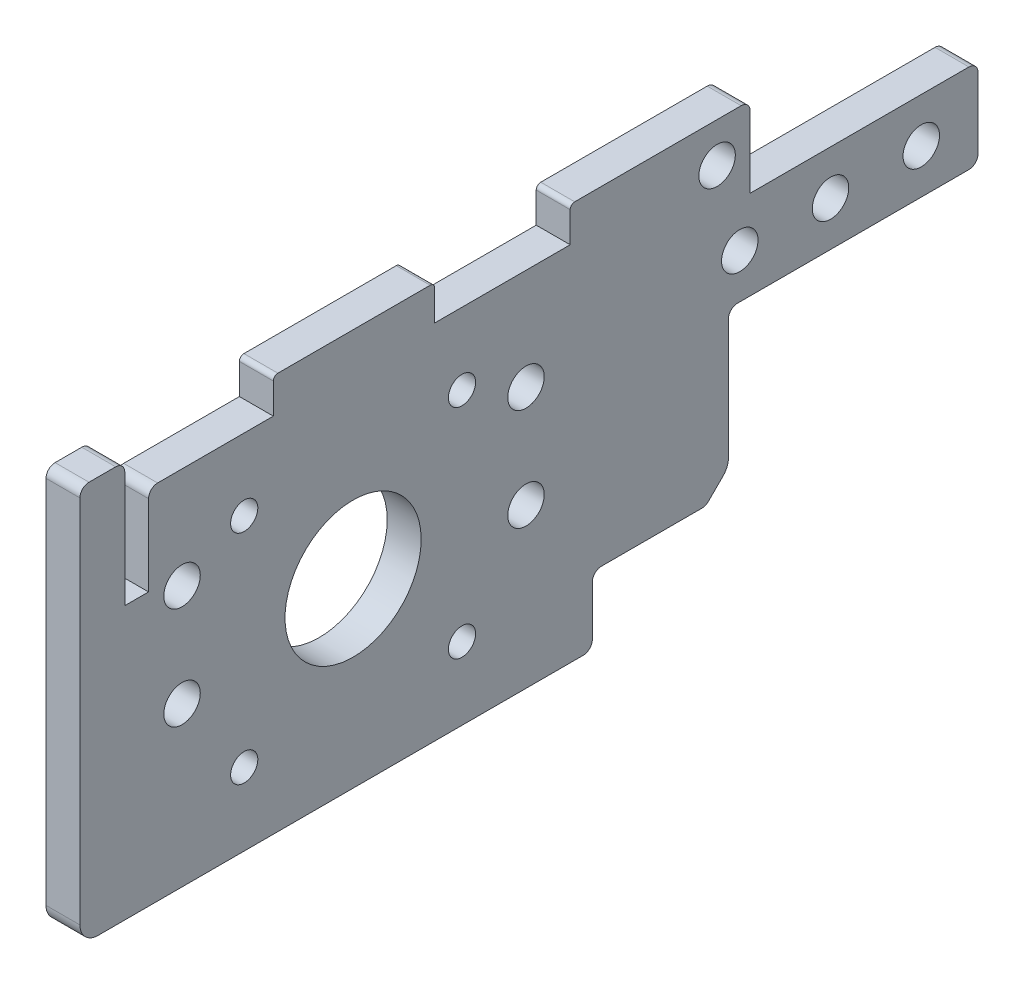
SolidWorks part; units mm, degrees
material "AISI Type A2 Tool Steel"
ref_plane "Front Plane" through (0, 0, 0) normal (0, 0, 1) x (1, 0, 0)
ref_plane "Top Plane" through (0, 0, 0) normal (0, 1, 0) x (1, 0, 0)
ref_plane "Right Plane" through (0, 0, 0) normal (1, 0, 0) x (0, 0, -1)
sketch "Top Layout" plane through (0, 0, 0) normal (0, 1, 0) x (1, 0, 0)
  line L0 (-114.046, -123.825) -> (-104.775, -123.825) construction
  line L1 (-104.775, -142.875) -> (-101.6, -142.875)
  line L2 (-104.775, -142.875) -> (-104.775, -104.775)
  line L3 (-104.775, -104.775) -> (-101.6, -104.775)
  line L4 (-101.6, -142.875) -> (-101.6, -104.775)
  line L5 (-104.775, -142.875) -> (-101.6, -104.775) construction
  line L6 (-104.775, -104.775) -> (-101.6, -142.875) construction
  line L7 (-19.05, -105.8164) -> (-101.6, -105.8164)
  line L8 (-19.05, -105.8164) -> (-19.05, -141.8336)
  line L9 (-19.05, -141.8336) -> (-101.6, -141.8336)
  line L10 (-101.6, -105.8164) -> (-101.6, -141.8336)
  line L11 (-19.05, -105.8164) -> (-101.6, -141.8336) construction
  line L12 (-19.05, -141.8336) -> (-101.6, -105.8164) construction
  line L13 (-133.096, -85.725) -> (-114.046, -85.725)
  line L14 (-133.096, -85.725) -> (-133.096, -161.925)
  line L15 (-133.096, -161.925) -> (-114.046, -161.925)
  line L16 (-114.046, -85.725) -> (-114.046, -161.925)
  line L17 (-133.096, -85.725) -> (-114.046, -161.925) construction
  line L18 (-133.096, -161.925) -> (-114.046, -85.725) construction
  line L19 (-104.775, -123.825) -> (0, -123.825) construction
  line L20 (0, -123.825) -> (0, 0) construction
  line L21 (-52.3528, -40.1717) -> (0, 0) construction
  line L22 (-70.6449, -16.3328) -> (-18.2922, 23.8388)
  line L23 (-34.0606, -64.0105) -> (18.2922, -23.8388)
  line L24 (-30.9251, 40.3023) -> (-122.2248, -29.7544)
  line L25 (-153.9748, -53.975) -> (-153.9748, -123.825)
  line L26 (-109.5248, -162.052) -> (109.5248, -162.052)
  line L27 (0, -162.052) -> (0, -123.825) construction
  line L28 (-109.5248, -162.052) -> (-109.5248, -20.0093) construction
  line L29 (-104.775, -142.875) -> (-104.775, -152.527)
  line L30 (-104.775, -152.527) -> (104.775, -152.527)
  line L31 (104.775, -104.775) -> (101.6, -104.775)
  line L32 (-144.4498, -73.025) -> (-109.5248, -73.025)
  line L33 (-144.4498, -73.025) -> (-144.4498, -123.825)
  line L34 (-144.4498, -123.825) -> (-109.5248, -123.825) construction
  line L35 (-109.5248, -73.025) -> (-109.5248, -162.052)
  line L36 (-144.4498, -73.025) -> (-109.5248, -123.825) construction
  line L37 (-144.4498, -123.825) -> (-109.5248, -73.025) construction
  line L38 (101.6, -142.875) -> (101.6, -104.775)
  line L39 (104.775, -142.875) -> (101.6, -142.875)
  line L40 (104.775, -142.875) -> (104.775, -104.775)
  line L41 (104.775, -142.875) -> (104.775, -152.527)
  line L42 (109.5248, -162.052) -> (109.5248, -20.0093) construction
  line L43 (30.9251, 40.3023) -> (122.2248, -29.7544)
  line L45 (19.05, -141.8336) -> (101.6, -141.8336)
  line L46 (101.6, -105.8164) -> (101.6, -141.8336)
  line L47 (19.05, -105.8164) -> (101.6, -105.8164)
  line L48 (19.05, -105.8164) -> (19.05, -141.8336)
  line L49 (133.096, -161.925) -> (114.046, -161.925)
  line L50 (114.046, -85.725) -> (114.046, -161.925)
  line L51 (133.096, -85.725) -> (114.046, -85.725)
  line L52 (133.096, -85.725) -> (133.096, -161.925)
  line L53 (144.4498, -123.825) -> (109.5248, -123.825) construction
  line L54 (109.5248, -73.025) -> (109.5248, -162.052)
  line L55 (144.4498, -73.025) -> (109.5248, -73.025)
  line L56 (144.4498, -73.025) -> (144.4498, -123.825)
  line L57 (-109.5248, -123.825) -> (-109.5248, -162.052) construction
  line L62 (-153.9748, -53.975) -> (-122.2248, -53.975)
  line L63 (-122.2248, -53.975) -> (-122.2248, -29.7544)
  line L64 (-144.4498, -123.825) -> (-153.9748, -123.825)
  line L65 (153.9748, -53.975) -> (153.9748, -123.825)
  line L66 (109.5248, -123.825) -> (109.5248, -162.052) construction
  line L67 (144.4498, -123.825) -> (153.9748, -123.825)
  line L68 (122.2248, -29.7544) -> (122.2248, -53.975)
  line L73 (-104.775, -104.775) -> (-104.775, -16.3647) construction
  line L74 (-95.25, -162.052) -> (-95.25, -9.0559) construction
  line L75 (-109.5248, -162.052) -> (-109.5248, -123.825) construction
  line L76 (109.5248, -162.052) -> (109.5248, -123.825) construction
  line L77 (122.2248, -53.975) -> (153.9748, -53.975)
  line L83 (104.775, -155.5496) -> (-104.775, -155.5496) construction
  line L88 (95.25, -162.052) -> (95.25, -9.0559) construction
  line L89 (104.775, -104.775) -> (104.775, -16.3647) construction
  line L92 (-104.775, -152.527) -> (-104.775, -162.052) construction
  line L93 (-14.605, -76.327) -> (14.605, -76.327)
  line L94 (-14.605, -76.327) -> (-14.605, -152.527)
  line L95 (-14.605, -152.527) -> (14.605, -152.527)
  line L96 (14.605, -76.327) -> (14.605, -152.527)
  line L97 (-14.605, -76.327) -> (14.605, -152.527) construction
  line L98 (-14.605, -152.527) -> (14.605, -76.327) construction
  line L99 (104.775, -152.527) -> (104.775, -162.052) construction
  line L100 (-19.05, -105.8164) -> (0, -105.8164) construction
  line L107 (0, -105.8164) -> (19.05, -105.8164) construction
  line L108 (104.775, -123.825) -> (114.046, -123.825) construction
  circle A0 centre (0, 0) radius 114.3
  circle A1 centre (0, 0) radius 6.35
  circle A2 centre (-52.3528, -40.1717) radius 17.8
  circle A3 centre (0, 0) radius 30.0482
  circle A4 centre (-52.3528, -40.1717) radius 30.0482
  arc A5 (-30.9251, 40.3023) -> (30.9251, 40.3023) centre (0, 0) cw
  point P2 (-103.1875, -123.825)
  point P7 (-60.325, -123.825)
  point P12 (-123.571, -123.825)
  point P30 (-126.9873, -98.425)
  point P35 (0, -114.427)
  point P53 (0, -152.527)
  dimension "D1" = 35.6
  dimension "D2" = 12.7
  dimension "D3" = 228.6
  dimension "D11" = 60.0964
  dimension "D12" = 50.8
  dimension "D14" = 52.5
  dimension "D4" = 3.175
  dimension "D5" = 19.05
  dimension "D6" = 76.2
  dimension "D7" = 82.55
  dimension "D8" = 38.1
  dimension "D9" = 104.775
  dimension "D10" = 18.0086
  dimension "D13" = 9.525
  dimension "D15" = 4.7498
  dimension "D16" = 9.525
  dimension "D17" = 9.652
  dimension "D18" = 50.8
  dimension "D19" = 12.446
  dimension "D20" = 65.9892
  dimension "D21" = 19.05
  dimension "D22" = 34.925
  dimension "D23" = 123.825
  dimension "D24" = 12.7
  dimension "D25" = 9.525
  dimension "D26" = 29.21
  dimension "D27" = 76.2
  dimension "D28" = 3.0226
sketch "Side Layout" plane through (0, 0, 0) normal (1, 0, 0) x (0, 0, -1)
  line L0 (0, -38.1) -> (0, 33.7344) construction
  line L1 (-114.3, -20.955) -> (114.3, -20.955)
  line L2 (-114.3, -20.955) -> (-114.3, -33.655)
  line L3 (-114.3, -33.655) -> (114.3, -33.655)
  line L4 (114.3, -20.955) -> (114.3, -33.655)
  line L5 (-114.3, -20.955) -> (114.3, -33.655) construction
  line L6 (-114.3, -33.655) -> (114.3, -20.955) construction
  line L7 (-9.525, -32.9406) -> (9.525, -32.9406)
  line L8 (-9.525, -32.9406) -> (-9.525, -38.1)
  line L9 (-9.525, -38.1) -> (9.525, -38.1)
  line L10 (9.525, -32.9406) -> (9.525, -38.1)
  line L11 (-9.525, -32.9406) -> (9.525, -38.1) construction
  line L12 (-9.525, -38.1) -> (9.525, -32.9406) construction
  line L13 (-11.9126, -29.3338) -> (11.9126, -29.3338)
  line L14 (-11.9126, -29.3338) -> (-11.9126, -32.9406)
  line L15 (-11.9126, -32.9406) -> (11.9126, -32.9406)
  line L16 (11.9126, -29.3338) -> (11.9126, -32.9406)
  line L17 (-11.9126, -29.3338) -> (11.9126, -32.9406) construction
  line L18 (-11.9126, -32.9406) -> (11.9126, -29.3338) construction
  line L19 (-6.35, -32.9406) -> (6.35, -32.9406)
  line L20 (-6.35, -32.9406) -> (-6.35, 33.7344)
  line L21 (-6.35, 33.7344) -> (6.35, 33.7344)
  line L22 (6.35, -32.9406) -> (6.35, 33.7344)
  line L23 (-6.35, -32.9406) -> (6.35, 33.7344) construction
  line L24 (-6.35, 33.7344) -> (6.35, -32.9406) construction
  line L25 (-162.052, 0) -> (-123.825, 0) construction
  line L26 (114.3, -33.655) -> (114.3, 0) construction
  line L27 (-142.875, 19.05) -> (-104.775, 19.05)
  line L28 (-40.1717, -9.525) -> (-40.1717, 5.4) construction
  line L29 (-142.875, 19.05) -> (-142.875, -19.05)
  line L30 (-142.875, -19.05) -> (-104.775, -19.05)
  line L31 (-104.775, 19.05) -> (-104.775, -19.05)
  line L32 (-142.875, 19.05) -> (-104.775, -19.05) construction
  line L33 (-142.875, -19.05) -> (-104.775, 19.05) construction
  line L34 (-130.175, -38.1) -> (-117.9516, -38.1) construction
  line L35 (-57.9717, -14.6) -> (-22.3717, -14.6)
  line L36 (-30.0482, -2.794) -> (30.0482, -2.794)
  line L37 (-30.0482, -2.794) -> (-30.0482, -20.955)
  line L38 (-30.0482, -20.955) -> (30.0482, -20.955)
  line L39 (30.0482, -2.794) -> (30.0482, -20.955)
  line L40 (-30.0482, -2.794) -> (30.0482, -20.955) construction
  line L41 (-30.0482, -20.955) -> (30.0482, -2.794) construction
  line L42 (-30.0482, -2.794) -> (-30.0482, 0) construction
  line L43 (-123.825, 0) -> (0, 0) construction
  line L44 (-57.9717, -14.6) -> (-57.9717, 25.4)
  line L45 (-57.9717, 25.4) -> (-22.3717, 25.4)
  line L46 (-22.3717, -14.6) -> (-22.3717, 25.4)
  line L47 (-19.05, 0) -> (19.05, 0)
  line L48 (-19.05, 0) -> (-19.05, -1.9812)
  line L49 (-19.05, -1.9812) -> (19.05, -1.9812)
  line L50 (19.05, 0) -> (19.05, -1.9812)
  line L51 (-19.05, 0) -> (19.05, -1.9812) construction
  line L52 (-19.05, -1.9812) -> (19.05, 0) construction
  line L53 (-70.2199, -3.175) -> (-10.1235, -3.175)
  line L54 (-70.2199, -3.175) -> (-70.2199, -15.875)
  line L55 (-70.2199, -15.875) -> (-10.1235, -15.875)
  line L56 (-10.1235, -3.175) -> (-10.1235, -15.875)
  line L57 (-70.2199, -3.175) -> (-10.1235, -15.875) construction
  line L58 (-70.2199, -15.875) -> (-10.1235, -3.175) construction
  line L59 (-40.1717, -9.525) -> (-40.1717, 0) construction
  line L60 (-57.9717, -14.6) -> (-22.3717, 25.4) construction
  line L61 (-57.9717, 25.4) -> (-22.3717, -14.6) construction
  line L62 (-22.3717, 0) -> (-57.9717, 0) construction
  line L63 (-137.8162, 0) -> (-123.825, -13.9912) construction
  line L64 (-139.065, 15.24) -> (-108.585, 15.24) construction
  line L65 (-139.065, 15.24) -> (-139.065, -15.24) construction
  line L66 (-139.065, -15.24) -> (-108.585, -15.24) construction
  line L67 (-108.585, 15.24) -> (-108.585, -15.24) construction
  line L68 (-139.065, 15.24) -> (-108.585, -15.24) construction
  line L69 (-139.065, -15.24) -> (-108.585, 15.24) construction
  line L70 (-137.8162, 0) -> (-123.825, 13.9912) construction
  line L71 (-123.825, -13.9912) -> (-109.8338, 0) construction
  line L72 (-123.825, 13.9912) -> (-109.8338, 0) construction
  line L73 (-137.8162, 0) -> (-109.8338, 0) construction
  line L74 (-123.825, -13.9912) -> (-123.825, 13.9912) construction
  line L75 (-6.35, 17.8594) -> (6.35, 17.8594)
  line L76 (114.3, 0) -> (-114.3, 0) construction
  line L77 (-22.3717, 19.05) -> (-6.35, 19.05) construction
  line L78 (-123.825, 38.1) -> (-97.9206, 38.1) construction
  line L79 (-19.05, -3.5814) -> (19.05, -3.5814)
  line L80 (-19.05, -3.5814) -> (-19.05, -1.9812)
  line L81 (-19.05, -1.9812) -> (19.05, -1.9812)
  line L82 (19.05, -3.5814) -> (19.05, -1.9812)
  line L83 (-19.05, -3.5814) -> (19.05, -1.9812) construction
  line L84 (-19.05, -1.9812) -> (19.05, -3.5814) construction
  line L85 (-8.7376, -16.7608) -> (8.7376, -16.7608)
  line L86 (-8.7376, -16.7608) -> (-8.7376, -29.3338)
  line L87 (-8.7376, -29.3338) -> (8.7376, -29.3338)
  line L88 (8.7376, -16.7608) -> (8.7376, -29.3338)
  line L89 (-8.7376, -16.7608) -> (8.7376, -29.3338) construction
  line L90 (-8.7376, -29.3338) -> (8.7376, -16.7608) construction
  line L91 (-8.7376, -3.5814) -> (8.7376, -3.5814)
  line L92 (-8.7376, -3.5814) -> (-8.7376, -16.1544)
  line L93 (-8.7376, -16.1544) -> (8.7376, -16.1544)
  line L94 (8.7376, -3.5814) -> (8.7376, -16.1544)
  line L95 (-8.7376, -3.5814) -> (8.7376, -16.1544) construction
  line L96 (-8.7376, -16.1544) -> (8.7376, -3.5814) construction
  circle A0 centre (-123.825, 0) radius 18.0086
  circle A1 centre (-123.825, 0) radius 38.1
  circle A2 centre (-139.065, 15.24) radius 1.905
  circle A3 centre (-108.585, 15.24) radius 1.905
  circle A4 centre (-108.585, -15.24) radius 1.905
  circle A5 centre (-139.065, -15.24) radius 1.905
  circle A6 centre (-137.8162, 0) radius 1.6002
  circle A7 centre (-123.825, 13.9912) radius 1.6002
  circle A8 centre (-109.8338, 0) radius 1.6002
  circle A9 centre (-123.825, -13.9912) radius 1.6002
  point P0 (0, -27.305)
  point P6 (0, -31.1372)
  point P7 (0, -35.5203)
  point P21 (0, 0.3969)
  point P32 (0, -11.8745)
  point P43 (0, -0.9906)
  point P55 (-40.1717, -9.525)
  point P72 (-40.1717, 5.4)
  point P88 (0, -23.0473)
  point P93 (0, -2.7813)
  point P102 (0, -9.8679)
  dimension "D17" = 3.81
  dimension "D18" = 3.2004
  dimension "D1" = 12.7
  dimension "D2" = 5.1594
  dimension "D3" = 19.05
  dimension "D4" = 3.6068
  dimension "D5" = 23.8252
  dimension "D6" = 12.7
  dimension "D7" = 18.161
  dimension "D8" = 1.9812
  dimension "D9" = 12.7
  dimension "D10" = 40
  dimension "D11" = 25.4
  dimension "D12" = 50.8
  dimension "D13" = 41.275
  dimension "D14" = 30.48
  dimension "D15" = 4.445
  dimension "D16" = 19.7866
  dimension "D19" = 15.875
  dimension "D20" = 6.35
  dimension "D21" = 38.1
  dimension "D22" = 1.6002
  dimension "D23" = 38.1
  dimension "D24" = 17.4752
  dimension "D25" = 12.573
ref_plane "Plane1" through (0, 25.4, 0) normal (0, 1, 0) x (1, 0, 0)
sketch "Sketch3" plane through (0, 25.4, 0) normal (0, 1, 0) x (1, 0, 0)
  line L0 (-104.775, -36.3747) -> (-30.9251, 20.2924)
  line L1 (-104.775, -104.775) -> (-104.775, -16.3647) construction
  line L2 (0, -200130.175) -> (0, 199882.0484) construction
  line L3 (-30.9251, 40.3023) -> (-122.2248, -29.7544) construction
  line L5 (-104.775, -36.3747) -> (-104.775, -77.6497)
  line L6 (-92.075, -77.6497) -> (-104.775, -77.6497)
  line L7 (30.9251, 20.2924) -> (104.775, -36.3747)
  line L8 (104.775, -77.6497) -> (92.075, -77.6497)
  line L9 (104.775, -36.3747) -> (104.775, -77.6497)
  line L11 (104.775, -104.775) -> (104.775, -16.3647) construction
  line L12 (30.9251, 40.3023) -> (122.2248, -29.7544) construction
  line L13 (92.075, -74.6536) -> (24.1423, -22.5271)
  line L14 (-32.2514, -66.3682) -> (20.1013, -26.1965)
  line L15 (-30.9251, 20.2924) -> (0, 44.022)
  line L16 (0, 44.022) -> (30.9251, 20.2924)
  line L17 (-92.075, -77.6497) -> (-92.075, -73.1917)
  line L19 (-92.075, -73.1917) -> (-52.3528, -73.1917)
  line L20 (92.075, -74.6536) -> (92.075, -77.6497)
  circle A0 centre (-52.3528, -40.1717) radius 17.8 construction
  circle A1 centre (-52.3528, -40.1717) radius 17.8
  circle A2 centre (0, 0) radius 6.35
  circle A3 centre (0, 0) radius 6.35 construction
  arc A4 (-52.3528, -73.1917) -> (-32.2514, -66.3682) centre (-52.3528, -40.1717) ccw
  arc A5 (20.1013, -26.1965) -> (24.1423, -22.5271) centre (0, 0) ccw
  arc A6 (30.9251, 20.2924) -> (-30.9251, 20.2924) centre (0, -20.01) ccw construction
  point P28 (0, 44.022)
  dimension "D1" = 33.02
  dimension "D5" = 50.8
  dimension "D2" = 41.275
  dimension "D3" = 34.925
  dimension "D4" = 12.7
  dimension "D6" = 38.1
ref_plane "Plane3" through (-104.775, 0, 0) normal (-1, 0, 0) x (0, 0, 1)
sketch "Sketch6" plane through (-104.775, 0, 0) normal (-1, 0, 0) x (0, 0, 1)
  line L0 (162.052, -25.4) -> (162.052, 25.4)
  line L1 (162.052, 25.4) -> (77.6497, 25.4)
  line L2 (36.3747, 25.4) -> (77.6497, 25.4) construction
  line L3 (147.7645, 11.1125) -> (162.052, 11.1125) construction
  line L4 (162.052, 0) -> (71.2997, 0) construction
  line L5 (77.6497, 25.4) -> (77.6497, 19.05)
  line L6 (77.6497, 19.05) -> (36.3747, 19.05)
  line L7 (36.3747, 19.05) -> (36.3747, 6.35)
  line L8 (36.3747, 6.35) -> (71.2997, 6.35)
  line L10 (99.6315, -3.175) -> (99.6315, 11.1125) construction
  line L11 (71.2997, -25.4) -> (162.052, -25.4)
  line L13 (71.2997, 6.35) -> (71.2997, -25.4)
  line L14 (152.527, -25.4) -> (152.527, 25.4) construction
  line L15 (99.6315, 11.1125) -> (99.6315, 25.4) construction
  line L16 (147.7645, 11.1125) -> (147.7645, 25.4) construction
  line L17 (94.869, -7.9375) -> (104.394, -7.9375) construction
  line L18 (94.869, -7.9375) -> (94.869, 25.4) construction
  line L19 (94.869, 25.4) -> (104.394, 25.4) construction
  line L20 (104.394, -7.9375) -> (104.394, 25.4) construction
  line L21 (94.869, -7.9375) -> (104.394, 25.4) construction
  line L22 (94.869, 25.4) -> (104.394, -7.9375) construction
  line L23 (147.7645, 11.1125) -> (147.7645, -3.175) construction
  line L24 (104.394, -7.9375) -> (123.825, -7.9375) construction
  line L25 (143.002, -7.9375) -> (152.527, -7.9375) construction
  line L26 (143.002, -7.9375) -> (143.002, 25.4) construction
  line L27 (143.002, 25.4) -> (152.527, 25.4) construction
  line L28 (152.527, -7.9375) -> (152.527, 25.4) construction
  line L29 (143.002, -7.9375) -> (152.527, 25.4) construction
  line L30 (143.002, 25.4) -> (152.527, -7.9375) construction
  line L31 (123.825, -7.9375) -> (152.527, -7.9375) construction
  line L32 (104.775, 19.05) -> (104.775, -19.05) construction
  line L34 (155.702, -25.4) -> (155.702, 25.4) construction
  circle A0 centre (109.8338, 0) radius 1.6002 construction
  circle A1 centre (123.825, 13.9912) radius 1.6002 construction
  circle A2 centre (137.8162, 0) radius 1.6002 construction
  circle A3 centre (123.825, -13.9912) radius 1.6002 construction
  circle A4 centre (109.8338, 0) radius 1.6002 construction
  circle A5 centre (123.825, 13.9912) radius 1.6002 construction
  circle A6 centre (137.8162, 0) radius 1.6002 construction
  circle A7 centre (123.825, -13.9912) radius 1.6002 construction
  circle A8 centre (123.825, 0) radius 18.0086 construction
  circle A9 centre (123.825, 0) radius 18.0086 construction
  circle A10 centre (123.825, 0) radius 9.525
  circle A11 centre (108.585, -15.24) radius 1.905 construction
  circle A12 centre (108.585, 15.24) radius 1.905 construction
  circle A13 centre (139.065, 15.24) radius 1.905 construction
  circle A14 centre (139.065, -15.24) radius 1.905 construction
  circle A15 centre (108.585, -15.24) radius 1.905
  circle A16 centre (108.585, 15.24) radius 1.905
  circle A17 centre (139.065, 15.24) radius 1.905
  circle A18 centre (139.065, -15.24) radius 1.905
  circle A19 centre (147.7645, 11.1125) radius 2.5527
  circle A26 centre (99.6315, 11.1125) radius 2.5527
  circle A27 centre (99.6315, -3.175) radius 2.5527
  circle A28 centre (147.7645, -3.175) radius 2.5527
  point P29 (0, 0)
  point P55 (99.6315, 8.7312)
  point P61 (147.7645, 8.7312)
  dimension "D4" = 19.05
  dimension "D7" = 5.1054
  dimension "D1" = 6.35
  dimension "D2" = 12.7
  dimension "D3" = 25.4
  dimension "D5" = 6.35
  dimension "D6" = 3.175
  dimension "D8" = 0.381
  dimension "D9" = 14.2875
  dimension "D10" = 9.525
  dimension "D12" = 33.3375
extrude "Side Plate Extrude" add sketch "Sketch6" along normal up to vertex (4.7498 mm away) up to point (-109.5248, 0, 73.025)
sketch "Sketch12" [suppressed] plane through (0, 19.05, 0) normal (0, 1, 0) x (1, 0, 0)
  line L0 (-104.775, -77.6497) -> (-104.775, -36.3747)
  line L1 (-104.775, -36.3747) -> (-92.075, -36.3747)
  line L3 (-92.075, -36.3747) -> (-92.075, -77.6497)
  line L5 (-92.075, -77.6497) -> (-104.775, -77.6497)
  line L6 (-98.425, -77.6497) -> (-98.425, -63.3622) construction
  line L7 (-98.425, -63.3622) -> (-98.425, -50.6622) construction
  line L8 (-98.425, -50.6622) -> (-98.425, -36.3747) construction
  line L10 (-98.425, -36.3747) -> (-104.775, -36.3747) construction
  circle A0 centre (-98.425, -63.3622) radius 2.5527
  circle A1 centre (-98.425, -50.6622) radius 2.5527
  dimension "D2" = 5.1054
  dimension "D1" = 12.7
  dimension "D3" = 12.7
sketch "Sketch15" plane through (-109.5248, 0, 0) normal (-1, 0, 0) x (0, 0, 1)
  line L0 (36.3747, 12.7) -> (44.3122, 12.7) construction
  line L1 (36.3747, 19.05) -> (36.3747, 6.35) construction
  line L2 (44.3122, 12.7) -> (57.0122, 12.7) construction
  line L3 (57.0122, 12.7) -> (69.7122, 12.7) construction
  line L4 (69.7122, 12.7) -> (77.6497, 12.7) construction
  line L5 (77.6497, 12.7) -> (77.6497, 19.05) construction
  circle A0 centre (44.3122, 12.7) radius 2.5527
  circle A1 centre (57.0122, 12.7) radius 2.5527
  circle A2 centre (69.7122, 12.7) radius 2.5527
  dimension "D1" = 5.1054
  dimension "D2" = 12.7
extrude "Custom Nutstrip Holes" cut sketch "Sketch15" against normal through all
ref_plane "Plane5" through (0, 0, 152.527) normal (0, 0, 1) x (1, 0, 0)
sketch "Sketch41" plane through (0, 0, 152.527) normal (0, 0, 1) x (1, 0, 0)
  line L0 (-104.775, -7.9375) -> (-104.775, 25.4) construction
  line L1 (-104.775, -7.9375) -> (-104.775, 12.7)
  line L2 (-104.775, -7.9375) -> (104.775, -7.9375)
  line L3 (104.775, -7.9375) -> (104.775, 12.7)
  line L4 (104.775, 25.4) -> (-104.775, 25.4)
  line L5 (0, -7.9375) -> (0, 25.4) construction
  line L6 (-104.775, 3.9624) -> (-100.0125, 3.9624) construction
  line L7 (-100.0125, 3.9624) -> (-100.0125, 25.4) construction
  line L8 (104.775, 3.9624) -> (100.0125, 3.9624) construction
  line L9 (100.0125, 3.9624) -> (100.0125, 25.4) construction
  line L10 (19.05, 20.6375) -> (23.8252, 20.6375) construction
  line L11 (19.05, 15.875) -> (78.5876, 15.875) construction
  line L12 (19.05, 15.875) -> (19.05, 25.4) construction
  line L13 (19.05, 25.4) -> (78.5876, 25.4) construction
  line L14 (78.5876, 15.875) -> (78.5876, 25.4) construction
  line L15 (19.05, 15.875) -> (78.5876, 25.4) construction
  line L16 (19.05, 25.4) -> (78.5876, 15.875) construction
  line L17 (23.8252, 20.6375) -> (38.1127, 20.6375) construction
  line L18 (38.1127, 20.6375) -> (52.4002, 20.6375) construction
  line L19 (52.4002, 20.6375) -> (66.6877, 20.6375) construction
  line L20 (-104.775, 25.4) -> (-112.395, 25.4)
  line L21 (-112.395, 25.4) -> (-112.395, 3.175)
  line L22 (-112.395, 3.175) -> (-109.5248, 3.175)
  line L23 (-109.5248, 3.175) -> (-109.5248, 12.7)
  line L24 (-109.5248, 12.7) -> (-104.775, 12.7)
  line L25 (-104.775, 12.7) -> (-104.775, 25.4) construction
  line L26 (104.775, 25.4) -> (112.395, 25.4)
  line L27 (112.395, 25.4) -> (112.395, 3.175)
  line L28 (112.395, 3.175) -> (109.5248, 3.175)
  line L29 (109.5248, 3.175) -> (109.5248, 12.7)
  line L30 (109.5248, 12.7) -> (104.775, 12.7)
  line L31 (104.775, 12.7) -> (104.775, 25.4) construction
  line L32 (-100.0125, 3.9624) -> (-87.3125, 3.9624) construction
  line L33 (-63.5, -1.5875) -> (0, -1.5875) construction
  line L34 (0, -1.5875) -> (63.5, -1.5875) construction
  line L35 (63.5, -1.5875) -> (63.5, -7.9375) construction
  circle A0 centre (-100.0125, 3.9624) radius 2.5527
  circle A1 centre (100.0125, 3.9624) radius 2.5527
  circle A2 centre (23.8252, 20.6375) radius 2.5527
  circle A3 centre (38.1127, 20.6375) radius 2.5527
  circle A4 centre (52.4002, 20.6375) radius 2.5527
  circle A5 centre (66.6877, 20.6375) radius 2.5527
  circle A6 centre (-66.6877, 20.6375) radius 2.5527
  circle A7 centre (-52.4002, 20.6375) radius 2.5527
  circle A8 centre (-38.1127, 20.6375) radius 2.5527
  circle A9 centre (-23.8252, 20.6375) radius 2.5527
  circle A10 centre (-87.3125, 3.9624) radius 2.5527
  circle A11 centre (87.3125, 3.9624) radius 2.5527
  circle A12 centre (-63.5, -1.5875) radius 2.5527
  circle A13 centre (63.5, -1.5875) radius 2.5527
  point P14 (48.8188, 20.6375)
  dimension "D3" = 5.1054
  dimension "D7" = 5.1054
  dimension "D1" = 21.4376
  dimension "D2" = 4.7625
  dimension "D4" = 9.525
  dimension "D5" = 59.5376
  dimension "D6" = 4.7752
  dimension "D8" = 14.2875
  dimension "D9" = 7.62
  dimension "D10" = 4.7498
  dimension "D11" = 12.7
  dimension "D12" = 9.525
  dimension "D13" = 19.05
  dimension "D14" = 12.7
  dimension "D15" = 6.35
  dimension "D16" = 63.5
sketch "Sketch43" plane through (-109.5248, 0, 0) normal (-1, 0, 0) x (0, 0, 1)
  line L1 (152.527, 12.7) -> (155.702, 12.7)
  line L2 (152.527, 12.7) -> (152.527, 25.4)
  line L3 (152.527, 25.4) -> (155.702, 25.4)
  line L4 (155.702, 12.7) -> (155.702, 25.4)
  line L5 (152.527, 12.7) -> (155.702, 25.4) construction
  line L6 (152.527, 25.4) -> (155.702, 12.7) construction
  line L7 (162.052, 25.4) -> (77.6497, 25.4) construction
  point P4 (154.1145, 19.05)
  dimension "D1" = 3.175
extrude "Cut-Extrude19" cut sketch "Sketch43" against normal through all
sketch "Sketch44" plane through (0, 25.4, 0) normal (0, 1, 0) x (1, 0, 0)
  line L0 (73.8315, -147.7645) -> (73.8315, -152.527) construction
  line L1 (92.075, -74.6536) -> (92.075, -77.6497) construction
  line L2 (-92.075, -77.6497) -> (-92.075, -73.1917) construction
  line L3 (0, -123.825) -> (0, 0) construction
  line L4 (-92.075, -73.1917) -> (-52.3528, -73.1917) construction
  line L5 (-104.775, -104.775) -> (-104.775, -16.3647) construction
  line L6 (-32.2514, -66.3682) -> (20.1013, -26.1965) construction
  line L21 (-104.775, -68.1247) -> (-104.775, -152.527)
  line L22 (-104.775, -152.527) -> (104.775, -152.527)
  line L23 (104.775, -152.527) -> (104.775, -68.1247)
  line L34 (-104.775, -99.6315) -> (-100.0125, -99.6315) construction
  line L35 (-104.775, -147.7645) -> (-100.0125, -147.7645) construction
  line L36 (0, -152.527) -> (0, -35.6178) construction
  line L38 (30.969, -147.7645) -> (45.2565, -147.7645) construction
  line L39 (45.2565, -147.7645) -> (59.544, -147.7645) construction
  line L40 (59.544, -147.7645) -> (73.8315, -147.7645) construction
  line L41 (23.8252, -152.527) -> (30.969, -152.527) construction
  line L42 (104.775, -152.527) -> (-104.775, -152.527) construction
  line L43 (30.969, -152.527) -> (38.1127, -152.527) construction
  line L44 (30.969, -152.527) -> (30.969, -147.7645) construction
  line L45 (-92.075, -77.6497) -> (-104.775, -77.6497) construction
  line L48 (-35.1507, -62.5899) -> (-8.9743, -42.504) construction
  line L49 (-8.9743, -42.504) -> (17.2021, -22.4182) construction
  line L50 (45.5313, -32.9364) -> (87.3125, -64.9962) construction
  line L51 (92.075, -74.6536) -> (24.1423, -22.5271) construction
  line L52 (104.775, -77.6497) -> (92.075, -77.6497) construction
  line L79 (-104.775, -68.1247) -> (-92.075, -68.1247)
  line L80 (-92.075, -68.1247) -> (-92.075, -63.6667)
  line L85 (21.8118, -8.7328) -> (92.075, -62.6476)
  line L86 (-38.0499, -58.8115) -> (14.3028, -18.6398)
  line L87 (-92.075, -63.6667) -> (-52.3528, -63.6667)
  line L88 (92.075, -62.6476) -> (92.075, -68.1247)
  line L89 (92.075, -68.1247) -> (104.775, -68.1247)
  circle A0 centre (-73.8315, -147.7645) radius 2.5527
  circle A1 centre (-59.544, -147.7645) radius 2.5527
  circle A2 centre (-45.2565, -147.7645) radius 2.5527
  circle A3 centre (-30.969, -147.7645) radius 2.5527
  circle A17 centre (-100.0125, -99.6315) radius 2.5527
  circle A18 centre (-100.0125, -147.7645) radius 2.5527
  circle A19 centre (100.0125, -147.7645) radius 2.5527
  circle A20 centre (100.0125, -99.6315) radius 2.5527
  circle A21 centre (30.969, -147.7645) radius 2.5527
  circle A22 centre (45.2565, -147.7645) radius 2.5527
  circle A23 centre (59.544, -147.7645) radius 2.5527
  circle A24 centre (73.8315, -147.7645) radius 2.5527
  circle A25 centre (-87.3125, -68.4292) radius 4.7625 construction
  circle A26 centre (-35.1507, -62.5899) radius 4.7625 construction
  circle A27 centre (-8.9743, -42.504) radius 4.7625 construction
  circle A28 centre (17.2021, -22.4182) radius 4.7625 construction
  circle A29 centre (45.5313, -32.9364) radius 4.7625 construction
  circle A30 centre (87.3125, -64.9962) radius 4.7625 construction
  circle A32 centre (-87.3125, -68.4292) radius 2.5527
  circle A33 centre (-35.1507, -62.5899) radius 2.5527
  circle A34 centre (-8.9743, -42.504) radius 2.5527 construction
  circle A35 centre (17.2021, -22.4182) radius 2.5527
  circle A36 centre (45.5313, -32.9364) radius 2.5527
  circle A37 centre (87.3125, -64.9962) radius 2.5527
  circle A38 centre (-97.155, -85.2697) radius 7.62 construction
  circle A39 centre (97.155, -85.2697) radius 7.62 construction
  circle A40 centre (24.5121, -32.4156) radius 7.62 construction
  arc A41 (20.1013, -26.1965) -> (24.1423, -22.5271) centre (0, 0) ccw construction
  circle A42 centre (-97.155, -85.2697) radius 2.5527
  circle A43 centre (24.5121, -32.4156) radius 2.5527
  circle A44 centre (97.155, -85.2697) radius 2.5527
  arc A56 (14.3028, -18.6398) -> (21.8118, -8.7328) centre (0, 0) ccw
  arc A57 (-52.3528, -63.6667) -> (-38.0499, -58.8115) centre (-52.3528, -40.1717) ccw
  point P4 (-104.775, -152.527)
  dimension "D2" = 5.1054
  dimension "D7" = 5.1054
  dimension "D8" = 15.24
  dimension "D3" = 9.525
  dimension "D9" = 9.525
  dimension "D4" = 4.7625
  dimension "D5" = 14.2875
  dimension "D6" = 9.525
  dimension "D1" = 4.7625
  dimension "D10" = 52.664
sketch "Sketch72" plane through (0, 25.4, 0) normal (0, 1, 0) x (1, 0, 0)
  line L0 (-104.775, -68.1247) -> (-104.775, -152.527) construction
  line L1 (-104.775, -152.527) -> (-109.5248, -152.527)
  line L2 (-104.775, -152.527) -> (-104.775, -135.0645)
  line L3 (-104.775, -135.0645) -> (-109.5248, -135.0645)
  line L4 (-109.5248, -152.527) -> (-109.5248, -135.0645)
  line L5 (-104.775, -152.527) -> (-109.5248, -135.0645) construction
  line L6 (-104.775, -135.0645) -> (-109.5248, -152.527) construction
  line L7 (-104.775, -152.527) -> (104.775, -152.527) construction
  line L8 (-77.0065, -152.527) -> (-73.8315, -147.7645) construction
  line L9 (-77.0065, -152.527) -> (-27.794, -152.527)
  line L10 (-77.0065, -152.527) -> (-77.0065, -155.5496)
  line L11 (-77.0065, -155.5496) -> (-27.794, -155.5496)
  line L12 (-27.794, -152.527) -> (-27.794, -155.5496)
  line L13 (-77.0065, -152.527) -> (-27.794, -155.5496) construction
  line L14 (-77.0065, -155.5496) -> (-27.794, -152.527) construction
  line L15 (-27.794, -152.527) -> (-30.969, -147.7645) construction
  line L16 (-77.0065, -152.527) -> (-77.0065, -147.7645) construction
  line L18 (-104.775, -93.5247) -> (-109.5248, -93.5247)
  line L19 (-104.775, -93.5247) -> (-104.775, -112.3315)
  line L20 (-104.775, -112.3315) -> (-109.5248, -112.3315)
  line L21 (-109.5248, -93.5247) -> (-109.5248, -112.3315)
  line L22 (-104.775, -93.5247) -> (-109.5248, -112.3315) construction
  line L23 (-104.775, -112.3315) -> (-109.5248, -93.5247) construction
  line L24 (0, -152.527) -> (-12.7, -152.527)
  line L25 (0, -152.527) -> (0, -155.5496)
  line L26 (0, -155.5496) -> (-12.7, -155.5496)
  line L27 (-12.7, -152.527) -> (-12.7, -155.5496)
  line L28 (0, -152.527) -> (-12.7, -155.5496) construction
  line L29 (0, -155.5496) -> (-12.7, -152.527) construction
  line L30 (-104.775, -68.1247) -> (-109.5248, -68.1247)
  line L31 (-104.775, -68.1247) -> (-104.775, -77.6497)
  line L32 (-104.775, -77.6497) -> (-109.5248, -77.6497)
  line L33 (-109.5248, -68.1247) -> (-109.5248, -77.6497)
  line L34 (-104.775, -68.1247) -> (-109.5248, -77.6497) construction
  line L35 (-104.775, -77.6497) -> (-109.5248, -68.1247) construction
  line L38 (-103.505, -155.5496) -> (-90.805, -155.5496)
  line L39 (-90.805, -152.527) -> (-90.805, -155.5496)
  line L40 (-103.505, -155.5496) -> (-103.505, -152.527)
  line L41 (-103.505, -155.5496) -> (-90.805, -152.527) construction
  line L42 (-103.505, -152.527) -> (-90.805, -152.527)
  line L43 (-77.0065, -147.7645) -> (-73.8315, -147.7645) construction
  line L44 (-103.505, -152.527) -> (-101.5221, -149.823) construction
  circle A0 centre (-100.0125, -147.7645) radius 2.5527 construction
  circle A1 centre (-73.8315, -147.7645) radius 2.5527 construction
  circle A2 centre (-30.969, -147.7645) radius 2.5527 construction
  point P4 (-107.1499, -143.7958)
  point P5 (-100.0125, -147.7645)
  point P16 (-52.4002, -154.0383)
  point P18 (-97.155, -154.0383)
  point P25 (-107.1499, -102.9281)
  point P34 (-6.35, -154.0383)
  point P39 (-107.1499, -72.8872)
  dimension "D1" = 4.7498
  dimension "D2" = 12.7
  dimension "D3" = 12.7
  dimension "D4" = 12.7
  dimension "D5" = 9.525
  dimension "D6" = 15.875
  dimension "D7" = 12.7
  dimension "D8" = 3.175
  dimension "D9" = 1.27
  dimension "D10" = 3.0226
sketch "Sketch73" plane through (-109.5248, 0, 0) normal (-1, 0, 0) x (0, 0, 1)
  line L1 (77.6497, 25.4) -> (93.5247, 25.4)
  line L2 (77.6497, 25.4) -> (77.6497, 30.1625)
  line L3 (77.6497, 30.1625) -> (93.5247, 30.1625)
  line L4 (93.5247, 25.4) -> (93.5247, 30.1625)
  line L5 (77.6497, 25.4) -> (93.5247, 30.1625) construction
  line L6 (77.6497, 30.1625) -> (93.5247, 25.4) construction
  line L7 (112.3315, 25.4) -> (135.0645, 25.4)
  line L8 (112.3315, 25.4) -> (112.3315, 30.1625)
  line L9 (112.3315, 30.1625) -> (135.0645, 30.1625)
  line L10 (135.0645, 25.4) -> (135.0645, 30.1625)
  line L11 (112.3315, 25.4) -> (135.0645, 30.1625) construction
  line L12 (112.3315, 30.1625) -> (135.0645, 25.4) construction
  line L13 (155.702, 25.4) -> (162.052, 25.4)
  line L14 (155.702, 25.4) -> (155.702, 30.1625)
  line L15 (155.702, 30.1625) -> (162.052, 30.1625)
  line L16 (162.052, 25.4) -> (162.052, 30.1625)
  line L17 (155.702, 25.4) -> (162.052, 30.1625) construction
  line L18 (155.702, 30.1625) -> (162.052, 25.4) construction
  point P4 (85.5872, 27.7812)
  point P10 (123.698, 27.7812)
  point P16 (158.877, 27.7812)
  dimension "D1" = 4.7625
extrude "Boss-Extrude28" add sketch "Sketch73" against normal through all
sketch "Sketch108" plane through (-104.775, 0, 0) normal (1, 0, 0) x (0, 0, -1)
  line L0 (-93.5247, 30.1625) -> (-77.6497, 30.1625) construction
  line L1 (-77.6497, 19.05) -> (-68.1247, 19.05)
  line L2 (-77.6497, 19.05) -> (-77.6497, 30.1625)
  line L3 (-77.6497, 30.1625) -> (-68.1247, 30.1625)
  line L4 (-68.1247, 19.05) -> (-68.1247, 30.1625)
  line L5 (-77.6497, 19.05) -> (-68.1247, 30.1625) construction
  line L6 (-77.6497, 30.1625) -> (-68.1247, 19.05) construction
  circle A0 centre (-72.8872, 24.6062) radius 2.5527
  circle A1 centre (-69.7122, 12.7) radius 2.5527 construction
  point P4 (-72.8872, 24.6062)
  dimension "D1" = 9.525
extrude "Boss-Extrude35" add sketch "Sketch108" against normal through all
sketch "Sketch90" plane through (-104.775, 0, 0) normal (1, 0, 0) x (0, 0, -1)
  line L0 (-162.052, 30.1625) -> (-155.702, 30.1625) construction
  line L1 (-152.4508, 12.7) -> (-155.7782, 12.7)
  line L2 (-152.4508, 12.7) -> (-152.4508, 25.273)
  line L3 (-152.4508, 30.1625) -> (-155.7782, 30.1625)
  line L4 (-155.7782, 12.7) -> (-155.7782, 30.1625)
  line L5 (-152.4508, 12.7) -> (-155.7782, 30.1625) construction
  line L6 (-152.4508, 30.1625) -> (-155.7782, 12.7) construction
  line L7 (-152.527, 12.7) -> (-155.702, 12.7) construction
  line L8 (-53.8372, 6.477) -> (-53.8372, 6.35) construction
  line L9 (-36.3747, 6.35) -> (-71.2997, 6.35) construction
  line L10 (-135.0645, 30.1625) -> (-112.3315, 30.1625) construction
  line L11 (-152.4508, 30.1625) -> (-134.9883, 30.1625)
  line L12 (-152.4508, 30.1625) -> (-152.4508, 25.273) construction
  line L13 (-152.4508, 25.273) -> (-134.9883, 25.273)
  line L14 (-134.9883, 30.1625) -> (-134.9883, 25.273)
  line L15 (-152.4508, 30.1625) -> (-134.9883, 25.273) construction
  line L16 (-152.4508, 25.273) -> (-134.9883, 30.1625) construction
  line L17 (-112.4077, 30.1625) -> (-93.4485, 30.1625)
  line L18 (-112.4077, 30.1625) -> (-112.4077, 25.273)
  line L19 (-112.4077, 25.273) -> (-93.4485, 25.273)
  line L20 (-93.4485, 30.1625) -> (-93.4485, 25.273)
  line L21 (-112.4077, 30.1625) -> (-93.4485, 25.273) construction
  line L22 (-112.4077, 25.273) -> (-93.4485, 30.1625) construction
  line L23 (-36.3747, 19.05) -> (-36.3747, 6.35) construction
  line L24 (-68.1247, 19.05) -> (-36.3747, 19.05)
  line L25 (-68.1247, 19.05) -> (-68.1247, 18.923) construction
  line L26 (-68.1247, 18.923) -> (-36.3747, 18.923)
  line L27 (-36.3747, 19.05) -> (-36.3747, 18.923)
  line L28 (-68.1247, 19.05) -> (-36.3747, 18.923) construction
  line L29 (-68.1247, 18.923) -> (-36.3747, 19.05) construction
  line L30 (-152.4508, 25.273) -> (-152.4508, 30.1625) construction
  line L31 (-36.3747, 6.477) -> (-71.2997, 6.477)
  line L32 (-36.3747, 6.477) -> (-36.3747, -25.4)
  line L33 (-36.3747, -25.4) -> (-71.2997, -25.4)
  line L34 (-71.2997, 6.477) -> (-71.2997, -25.4)
  line L35 (-36.3747, 6.477) -> (-71.2997, -25.4) construction
  line L36 (-36.3747, -25.4) -> (-71.2997, 6.477) construction
  line L37 (-155.702, 21.4312) -> (-155.7782, 21.4312) construction
  line L38 (-155.702, 12.7) -> (-155.702, 30.1625) construction
  line L39 (-152.527, 19.05) -> (-152.4508, 19.05) construction
  line L40 (-152.527, 25.4) -> (-152.527, 12.7) construction
  line L41 (-143.7196, 25.273) -> (-143.7196, 25.4) construction
  line L42 (-152.527, 25.4) -> (-135.0645, 25.4) construction
  line L43 (-135.0645, 25.4) -> (-134.9883, 25.4) construction
  line L44 (-112.3315, 27.7812) -> (-112.4077, 27.7812) construction
  line L45 (-112.3315, 30.1625) -> (-112.3315, 25.4) construction
  line L46 (-102.9281, 25.4) -> (-102.9281, 25.273) construction
  line L47 (-112.3315, 25.4) -> (-93.5247, 25.4) construction
  line L48 (-93.5247, 25.4) -> (-93.4485, 25.4) construction
  line L49 (-71.2997, -25.4) -> (-162.052, -25.4) construction
  line L50 (-71.2997, 6.35) -> (-71.2997, -25.4) construction
  line L51 (-68.1247, 19.05) -> (-68.1247, 30.1625) construction
  line L52 (-93.5247, 30.1625) -> (-68.1247, 30.1625) construction
  line L53 (-68.2517, 30.1625) -> (-68.1247, 30.1625)
  line L54 (-68.2517, 30.1625) -> (-68.2517, 18.923)
  line L55 (-68.2517, 18.923) -> (-68.1247, 18.923)
  line L56 (-68.1247, 30.1625) -> (-68.1247, 19.05)
  line L57 (-68.2517, 30.1625) -> (-68.1247, 18.923) construction
  line L58 (-68.2517, 18.923) -> (-68.1247, 30.1625) construction
  line L59 (-68.1247, 19.05) -> (-68.1247, 18.923) construction
  point P4 (-154.1145, 21.4312)
  point P10 (-154.1145, 12.7)
  point P17 (-143.7196, 27.7177)
  point P22 (-102.9281, 27.7178)
  point P29 (-52.2497, 18.9865)
  point P37 (-53.8372, -9.4615)
  point P72 (-68.1882, 24.5427)
  dimension "D1" = 0.0762
  dimension "D2" = 0.127
extrude "Side Plate Tolerences" cut sketch "Sketch90" against normal through all
chamfer "Chamfer8" distance 12.7 1 edges at (-107.1499, -25.4, 71.2997)
fillet "Fillet15" radius 2.54 3 edges at (-107.1499, -12.7, 71.2997) (-107.1499, -25.4, 83.9997) (-107.1499, -25.4, 162.052)
fillet "Fillet26" radius 1.27 7 edges at (-107.1499, 6.477, 36.3747) (-107.1499, 18.923, 36.3747) (-107.1499, 30.1625, 68.2517) (-107.1499, 25.273, 152.4508) (-107.1499, 30.1625, 155.7782) (-107.1499, 30.1625, 162.052) (-107.1499, 6.477, 71.2997)
fillet "Fillet29" radius 0.635 3 edges at (-107.1499, 30.1625, 93.4485) (-107.1499, 30.1625, 112.4077) (-107.1499, 30.1625, 134.9883)
sketch "Sketch109" plane through (-104.775, 0, 0) normal (1, 0, 0) x (0, 0, -1)
  line L0 (-85.0518, -25.4) -> (-159.512, -25.4) construction
  line L1 (-90.3497, -25.4) -> (-71.2997, -25.4)
  line L2 (-90.3497, -25.4) -> (-90.3497, -15.875)
  line L3 (-90.3497, -15.875) -> (-71.2997, -15.875)
  line L4 (-71.2997, -25.4) -> (-71.2997, -15.875)
  line L5 (-90.3497, -25.4) -> (-71.2997, -15.875) construction
  line L6 (-90.3497, -15.875) -> (-71.2997, -25.4) construction
  line L7 (-71.2997, 5.207) -> (-71.2997, -11.6479) construction
  point P4 (-80.8247, -20.6375)
  dimension "D1" = 9.525
  dimension "D2" = 19.05
extrude "Cut-Extrude20" cut sketch "Sketch109" against normal through all
fillet "Fillet30" radius 1.27 3 edges at (-107.1499, -25.4, 90.3497) (-107.1499, -15.875, 90.3497) (-107.1499, -15.875, 74.4747)
